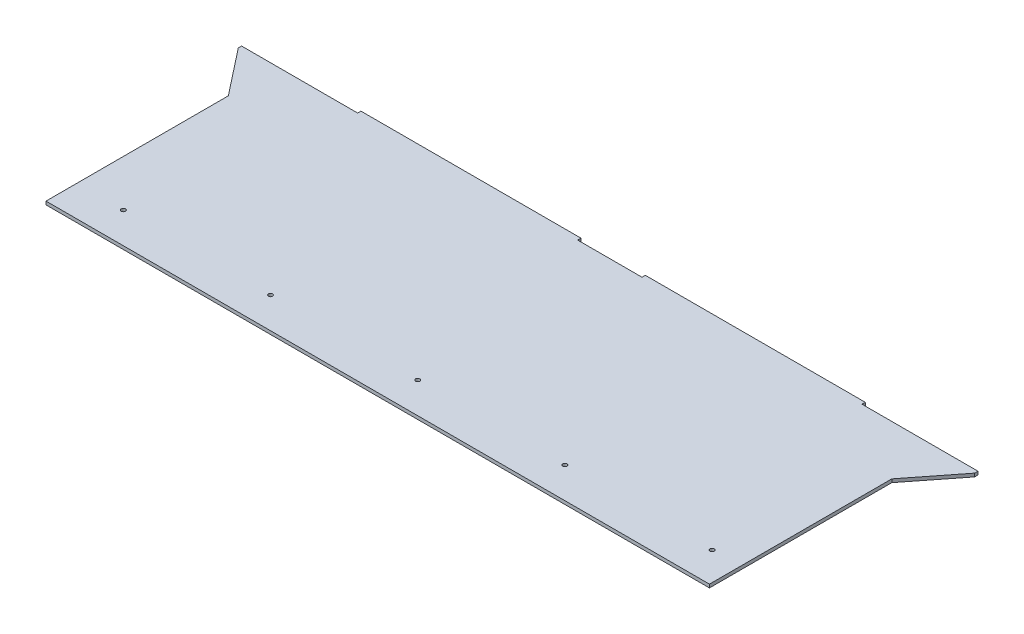
SolidWorks part; units mm, degrees
material "6061-T6 (SS)"
ref_plane "X-Y Datum" through (0, 0, 0) normal (0, 0, 1) x (1, 0, 0)
ref_plane "X-Z Datum" through (0, 0, 0) normal (0, 1, 0) x (1, 0, 0)
ref_plane "Y-Z Datum" through (0, 0, 0) normal (1, 0, 0) x (0, 0, -1)
sketch "Sketch1" plane through (0, 0, 0) normal (0, 1, 0) x (1, 0, 0)
  line L1 (-317.6778, 111.125) -> (317.6778, 111.125)
  line L2 (-317.6778, 111.125) -> (-317.6778, -111.125)
  line L3 (-317.6778, -111.125) -> (317.6778, -111.125)
  line L4 (317.6778, 111.125) -> (317.6778, -111.125)
  line L5 (-317.6778, 111.125) -> (317.6778, -111.125) construction
  line L6 (-317.6778, -111.125) -> (317.6778, 111.125) construction
  point P0 (0, 0)
  dimension "D1" = 635.3556
  dimension "D2" = 222.25
extrude "Boss-Extrude1" add sketch "Sketch1" along normal mid plane 3.175
sketch "Sketch2" plane through (0, 0, -111.125) normal (0, 0, -1) x (-1, 0, 0)
  line L0 (-241.4778, -1.5875) -> (-241.4778, 1.5875) construction
  line L1 (241.4778, -1.5875) -> (241.4778, 1.5875)
  line L2 (-241.4778, -1.5875) -> (-241.4778, 1.5875)
  line L3 (-241.4778, -1.5875) -> (-241.4778, 1.5875)
  line L4 (241.4778, -1.5875) -> (241.4778, 1.5875) construction
  line L5 (241.4778, -1.5875) -> (241.4778, 1.5875)
  line L20 (-317.6778, -1.5875) -> (317.6778, -1.5875) construction
  line L21 (-241.4778, -1.5875) -> (-30.8229, -1.5875)
  line L22 (30.8229, -1.5875) -> (241.4778, -1.5875)
  line L40 (30.8229, -1.5875) -> (30.8229, 1.5875)
  line L41 (30.8229, 1.5875) -> (241.4778, 1.5875)
  line L57 (-241.4778, 1.5875) -> (-30.8229, 1.5875)
  line L58 (-30.8229, 1.5875) -> (-30.8229, -1.5875)
  line M22 (-317.6778, -1.5875) -> (317.6778, -1.5875)
  line M24 (317.6778, 1.5875) -> (-317.6778, 1.5875)
extrude "Boss-Extrude2" add sketch "Sketch2" along normal blind 3.175 contours L58 L2 M24 M22 | L40 L1 M22 M24 region at (-136.1504, 0, -111.125) region at (136.1504, 0, -111.125)
sketch "Sketch3" plane through (0, 1.5875, 0) normal (0, 1, 0) x (1, 0, 0)
  line L0 (-317.6778, 111.125) -> (-352.6028, 111.125)
  line L1 (-352.6028, 111.125) -> (-352.6028, 107.95)
  line L2 (-352.6028, 107.95) -> (-317.6778, 63.5)
  line L3 (-317.6778, 111.125) -> (-317.6778, -111.125) construction
  line L16 (317.6778, -111.125) -> (317.6778, 111.125)
  line L17 (317.6778, 111.125) -> (241.4778, 111.125)
  line L18 (241.4778, 111.125) -> (241.4778, 114.3)
  line L19 (30.8229, 114.3) -> (30.8229, 111.125)
  line L20 (30.8229, 111.125) -> (-30.8229, 111.125)
  line L21 (-30.8229, 111.125) -> (-30.8229, 114.3)
  line L22 (-241.4778, 114.3) -> (-241.4778, 111.125)
  line L23 (-241.4778, 111.125) -> (-317.6778, 111.125)
  line L24 (241.4778, 114.3) -> (30.8229, 114.3)
  line L25 (241.4778, 114.3) -> (30.8229, 114.3)
  line L26 (-317.6778, 111.125) -> (-317.6778, -111.125)
  line L27 (-317.6778, -111.125) -> (317.6778, -111.125)
  line L38 (-317.6778, 111.125) -> (-317.6778, 63.5)
  line L40 (-30.8229, 114.3) -> (-241.4778, 114.3)
  line L41 (-30.8229, 114.3) -> (-241.4778, 114.3)
  line M26 (-317.6778, 111.125) -> (-317.6778, -111.125)
  dimension "D1" = 34.925
  dimension "D2" = 3.175
  dimension "D3" = 44.45
  dimension "D4" = 0
extrude "Boss-Extrude3" add sketch "Sketch3" against normal blind 3.175 contours L1 L2 L0 M26 region at (-330.0471, 1.5875, -95.1839)
mirror "Mirror1" about plane through (0, 0, 0) normal (1, 0, 0) of "Boss-Extrude3"
sketch "Sketch4" plane through (0, 1.5875, 0) normal (0, 1, 0) x (1, 0, 0)
  line L0 (-273.2278, -111.125) -> (-273.2278, -81.534)
  line L1 (-317.6778, -111.125) -> (317.6778, -111.125) construction
  line L2 (-273.2278, -81.534) -> (-317.6778, -81.534)
  line L3 (-317.6778, 63.5) -> (-317.6778, -111.125) construction
  circle A0 centre (-273.2278, -81.534) radius 2.025
extrude "Cut-Extrude1" cut sketch "Sketch4" against normal blind 10 contours L0 A0 L2 | L2 A0 L0 region at (-274.0872, 1.5875, 82.3934) region at (-272.9413, 1.5875, 81.2475)
pattern_linear "LPattern1" count 5 spacing 140.97 along (1, 0, 0) of "Cut-Extrude1"
